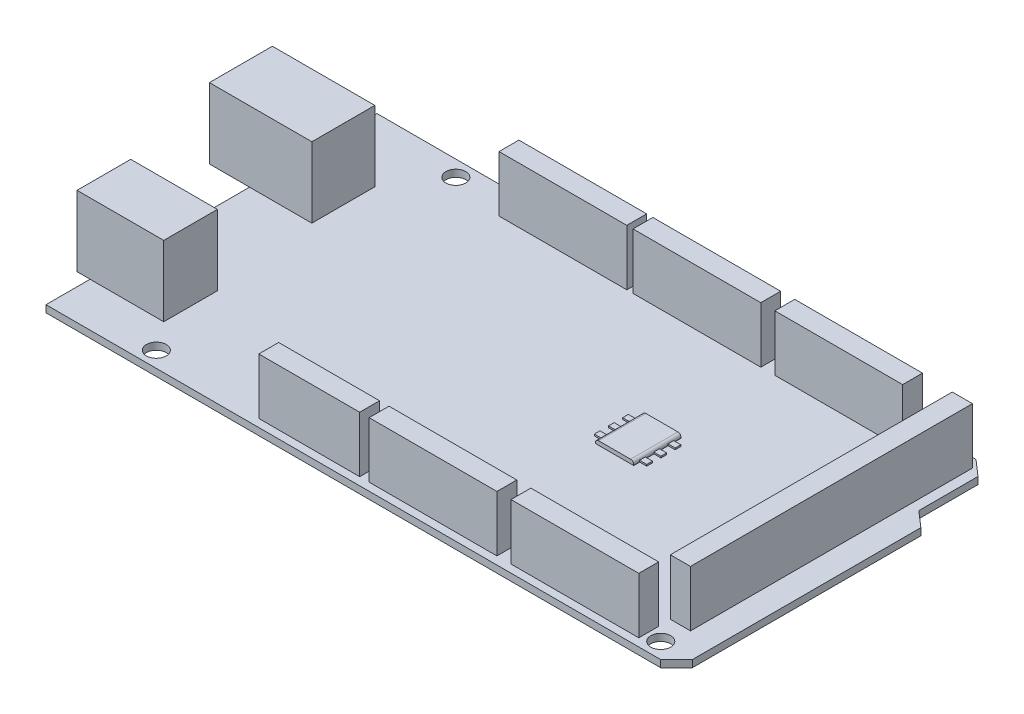
SolidWorks part; units mm, degrees
ref_plane "Front" through (0, 0, 0) normal (0, 0, 1) x (1, 0, 0)
ref_plane "Top" through (0, 0, 0) normal (0, 1, 0) x (1, 0, 0)
ref_plane "Right" through (0, 0, 0) normal (1, 0, 0) x (0, 0, -1)
sketch "Sketch2" plane through (0, 0, 0) normal (0, 1, 0) x (1, 0, 0)
  line L1 (0, 0) -> (101.6, 0)
  line L2 (0, 0) -> (0, 53.34)
  line L3 (0, 53.34) -> (101.6, 53.34)
  line L4 (101.6, 0) -> (101.6, 53.34)
  dimension "D1" = 101.6
  dimension "D2" = 53.34
extrude "Boss-Extrude1" add sketch "Sketch2" along normal blind 1.14
sketch "Sketch3" plane through (0, 1.14, 0) normal (0, 1, 0) x (1, 0, 0)
  line L0 (0, 26.67) -> (101.6, 26.67) construction
  line L1 (0, 53.34) -> (0, 0) construction
  line L2 (101.6, 0) -> (101.6, 53.34) construction
  line L3 (50.8, 0) -> (50.8, 53.34) construction
  line L4 (0, 0) -> (101.6, 0) construction
  line L5 (101.6, 53.34) -> (0, 53.34) construction
  circle A0 centre (15.24, 50.8) radius 1.6
  circle A1 centre (15.24, 2.54) radius 1.6
  dimension "D1" = 3.2
  dimension "D2" = 15.24
  dimension "D3" = 2.54
extrude "Cut-Extrude1" cut sketch "Sketch3" against normal through all
sketch "Sketch4" plane through (0, 1.14, 0) normal (0, 1, 0) x (1, 0, 0)
  line L0 (45.72, 52.07) -> (66.31, 52.07)
  line L1 (24.13, 52.07) -> (44.72, 52.07)
  line L2 (24.13, 52.07) -> (24.13, 48.87)
  line L3 (24.13, 48.87) -> (44.72, 48.87)
  line L4 (44.72, 52.07) -> (44.72, 48.87)
  line L5 (66.31, 52.07) -> (66.31, 48.87)
  line L6 (45.72, 48.87) -> (66.31, 48.87)
  line L7 (45.72, 52.07) -> (45.72, 48.87)
  line L8 (68.58, 52.07) -> (89.17, 52.07)
  line L9 (89.17, 52.07) -> (89.17, 48.87)
  line L10 (68.58, 48.87) -> (89.17, 48.87)
  line L11 (68.58, 52.07) -> (68.58, 48.87)
  line L12 (73.66, 4.47) -> (94.25, 4.47)
  line L13 (94.25, 4.47) -> (94.25, 1.27)
  line L14 (73.66, 1.27) -> (94.25, 1.27)
  line L15 (73.66, 4.47) -> (73.66, 1.27)
  line L16 (50.8, 4.47) -> (71.39, 4.47)
  line L17 (71.39, 4.47) -> (71.39, 1.27)
  line L18 (50.8, 1.27) -> (71.39, 1.27)
  line L19 (50.8, 4.47) -> (50.8, 1.27)
  line L20 (33.02, 4.47) -> (49.276, 4.47)
  line L21 (49.276, 4.47) -> (49.276, 1.27)
  line L22 (33.02, 1.27) -> (49.276, 1.27)
  line L23 (33.02, 4.47) -> (33.02, 1.27)
  line L25 (101.6, 53.34) -> (0, 53.34) construction
  line L26 (0, 0) -> (101.6, 0) construction
  circle A0 centre (15.24, 2.54) radius 1.6 construction
  circle A1 centre (15.24, 50.8) radius 1.6 construction
  point P24 (33.02, 2.87)
  dimension "D6" = 8.89
  dimension "D1" = 30.48
  dimension "D7" = 53.34
  dimension "D9" = 1.27
  dimension "D2" = 20.59
  dimension "D3" = 17.78
  dimension "D4" = 35.56
  dimension "D5" = 58.42
  dimension "D8" = 1.27
  dimension "D10" = 1.27
  dimension "D11" = 1.27
  dimension "D12" = 1.27
  dimension "D13" = 1.27
  dimension "D14" = 3.2
  dimension "D15" = 3.2
  dimension "D16" = 3.2
  dimension "D17" = 3.2
  dimension "D18" = 3.2
  dimension "D19" = 3.2
  dimension "D20" = 16.256
extrude "Boss-Extrude2" add sketch "Sketch4" along normal blind 9
sketch "Sketch5" plane through (0, 1.14, 0) normal (0, 1, 0) x (1, 0, 0)
  line L1 (101.6, 0) -> (99.06, 0)
  line L2 (101.6, 0) -> (101.6, 2.54)
  line L4 (99.06, 41.5843) -> (99.06, 51.1213)
  line L5 (101.6, 39.37) -> (99.06, 41.5843)
  line L6 (99.06, 0) -> (101.6, 0)
  line L7 (101.6, 39.37) -> (101.6, 53.34)
  line L9 (101.6, 0) -> (101.6, 2.54)
  line L10 (99.076, 51.1073) -> (96.536, 53.3216)
  line L11 (99.06, 0) -> (101.6, 2.54)
  line L12 (101.6, 53.34) -> (101.6055, 53.3418)
  line L14 (101.6, 53.3216) -> (101.6055, 53.3216)
  line L15 (96.536, 53.3216) -> (96.536, 57.5595)
  line L16 (96.536, 57.5595) -> (101.6055, 57.5595)
  line L17 (101.6055, 53.3216) -> (101.6055, 57.5595)
  dimension "D2" = 39.37
extrude "Cut-Extrude2" cut sketch "Sketch5" against normal through all
sketch "Sketch6" plane through (0, 1.14, 0) normal (0, 1, 0) x (1, 0, 0)
  line L0 (0, 0) -> (99.06, 0) construction
  line L1 (96.536, 53.34) -> (0, 53.34) construction
  circle A0 centre (96.52, 2.54) radius 1.6
  circle A1 centre (91.44, 50.8) radius 1.6
  circle A2 centre (15.24, 2.54) radius 1.6 construction
  circle A3 centre (15.24, 50.8) radius 1.6 construction
  dimension "D1" = 3.2
  dimension "D2" = 3.2
  dimension "D4" = 2.54
  dimension "D5" = 81.28
  dimension "D6" = 76.2
  dimension "D3" = 2.54
extrude "Cut-Extrude3" cut sketch "Sketch6" against normal through all
sketch "Sketch7" plane through (0, 1.14, 0) normal (0, 1, 0) x (1, 0, 0)
  line L1 (94.2041, 6.4033) -> (97.4493, 6.4033)
  line L2 (94.2041, 6.4033) -> (94.2041, 51.8366)
  line L3 (94.2041, 51.8366) -> (97.4493, 51.8366)
  line L4 (97.4493, 6.4033) -> (97.4493, 51.8366)
extrude "Boss-Extrude3" add sketch "Sketch7" along normal blind 9
sketch "Sketch8" plane through (0, 1.14, 0) normal (0, 1, 0) x (1, 0, 0)
  line L0 (0, 53.34) -> (0, 0) construction
  line L1 (-6.47, 32.7987) -> (10.04, 32.7987)
  line L2 (-6.47, 32.7987) -> (-6.47, 42.9489)
  line L3 (-6.47, 42.9489) -> (10.04, 42.9489)
  line L4 (10.04, 32.7987) -> (10.04, 42.9489)
  line L6 (-2.1, 7.1016) -> (11.87, 7.1016)
  line L7 (-2.1, 7.1016) -> (-2.1, 15.752)
  line L8 (-2.1, 15.752) -> (11.87, 15.752)
  line L9 (11.87, 7.1016) -> (11.87, 15.752)
  dimension "D1" = 6.47
  dimension "D2" = 2.1
  dimension "D3" = 13.97
  dimension "D4" = 16.51
extrude "Boss-Extrude4" add sketch "Sketch8" along normal blind 11.36
sketch "Sketch9" plane through (-2.1, 0, 0) normal (-1, 0, 0) x (0, 0, 1)
  line L0 (-11.4268, 12.5) -> (-11.4268, 1.14) construction
  line L1 (-15.752, 12.5) -> (-7.1016, 12.5) construction
  line L2 (-15.752, 1.14) -> (-7.1016, 1.14) construction
  circle A0 centre (-11.4268, 7.8705) radius 3.2177
  circle A1 centre (-11.4268, 7.8705) radius 1.1827
extrude "Cut-Extrude4" cut sketch "Sketch9" against normal blind 11.36
sketch "Sketch10" plane through (-6.47, 0, 0) normal (-1, 0, 0) x (0, 0, 1)
  line L0 (-37.8738, 12.5) -> (-37.8738, 1.14) construction
  line L1 (-42.9489, 12.5) -> (-32.7987, 12.5) construction
  line L2 (-42.9489, 1.14) -> (-32.7987, 1.14) construction
  line L4 (-41.0488, 9.6378) -> (-34.6988, 9.6378)
  line L5 (-41.0488, 9.6378) -> (-41.0488, 4.0757)
  line L6 (-41.0488, 4.0757) -> (-34.6988, 4.0757)
  line L7 (-34.6988, 9.6378) -> (-34.6988, 4.0757)
  line L8 (-40.4406, 6.0584) -> (-35.2398, 6.0584)
  line L9 (-40.4406, 6.0584) -> (-40.4406, 4.6059)
  line L10 (-40.4406, 4.6059) -> (-35.2398, 4.6059)
  line L11 (-35.2398, 6.0584) -> (-35.2398, 4.6059)
  dimension "D1" = 6.35
  dimension "D2" = 3.175
extrude "Cut-Extrude5" cut sketch "Sketch10" against normal blind 11.36
chamfer "Chamfer1" distance 1.524 angle 45 2 edges at (-0.79, 9.6378, -34.6988) (-0.79, 9.6378, -41.0488)
sketch "Sketch11" plane through (0, 1.14, 0) normal (0, 1, 0) x (1, 0, 0)
  line L0 (96.536, 53.34) -> (0, 53.34) construction
  line L1 (63.63, 32.52) -> (69.8062, 32.52)
  line L2 (63.63, 32.52) -> (63.63, 24.9)
  line L3 (63.63, 24.9) -> (69.8062, 24.9)
  line L4 (69.8062, 32.52) -> (69.8062, 24.9)
  circle A0 centre (15.24, 50.8) radius 1.6 construction
  dimension "D1" = 48.39
  dimension "D2" = 20.82
  dimension "D3" = 7.62
extrude "Boss-Extrude5" add sketch "Sketch11" along normal blind 0.635
sketch "Sketch12" plane through (0, 1.14, 0) normal (0, 1, 0) x (1, 0, 0)
  line L0 (62.4818, 29.0669) -> (62.4818, 28.1512)
  line L1 (62.4818, 31.3529) -> (70.9386, 31.3529)
  line L2 (62.4818, 31.3529) -> (62.4818, 30.4372)
  line L3 (62.4818, 30.4372) -> (70.9386, 30.4372)
  line L4 (70.9386, 31.3529) -> (70.9386, 30.4372)
  line L5 (62.4818, 29.0669) -> (70.9386, 29.0669)
  line L6 (70.9386, 29.0669) -> (70.9386, 28.1512)
  line L7 (62.4818, 28.1512) -> (70.9386, 28.1512)
  line L8 (62.4818, 26.7809) -> (62.4818, 25.8652)
  line L9 (62.4818, 26.7809) -> (70.9386, 26.7809)
  line L10 (70.9386, 26.7809) -> (70.9386, 25.8652)
  line L11 (62.4818, 25.8652) -> (70.9386, 25.8652)
  dimension "D1" = 3
extrude "Boss-Extrude6" add sketch "Sketch12" along normal blind 0.254
fillet "Fillet1" radius 0.508 2 edges at (69.8062, 1.775, -28.71) (63.63, 1.775, -28.71)
